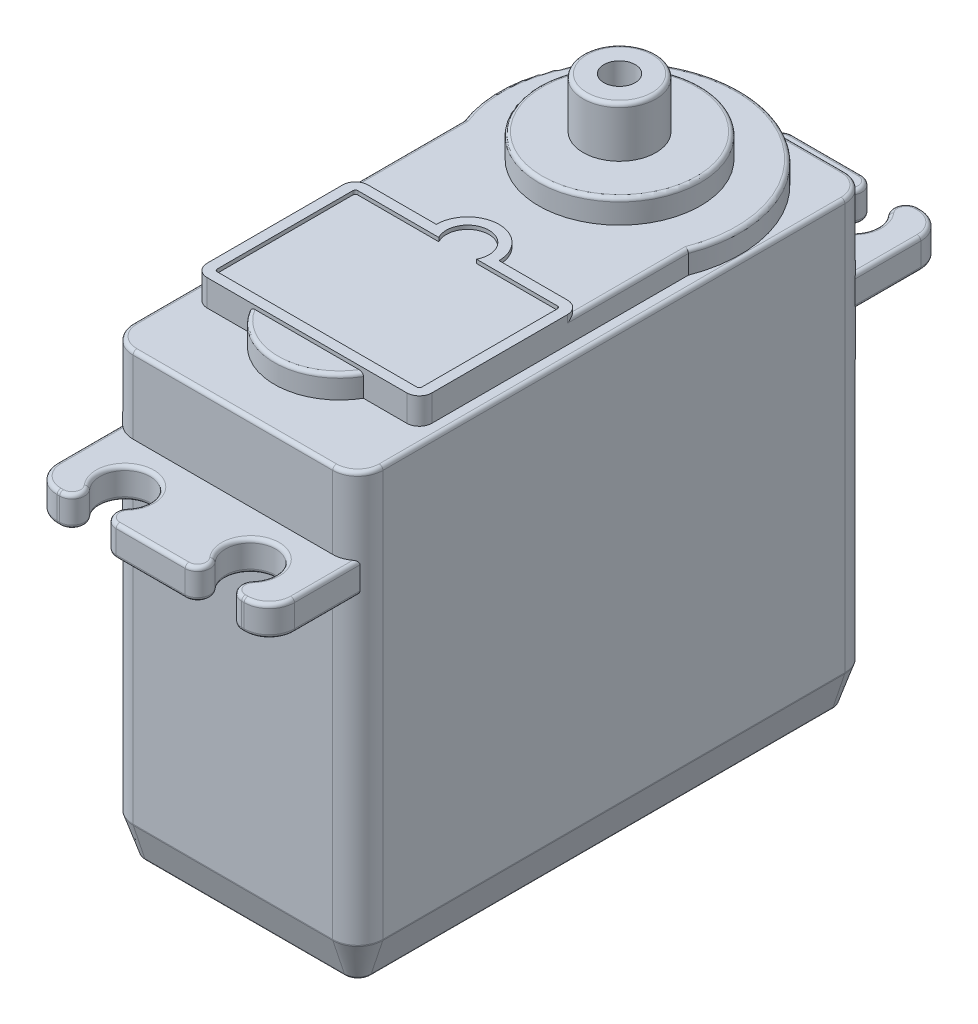
SolidWorks part; units mm, degrees
material "ABS"
ref_plane "Plan de face" through (0, 0, 0) normal (0, 0, 1) x (1, 0, 0)
ref_plane "Plan de dessus" through (0, 0, 0) normal (0, 1, 0) x (1, 0, 0)
ref_plane "Plan de droite" through (0, 0, 0) normal (1, 0, 0) x (0, 0, -1)
sketch "Esquisse1" plane through (0, 0, 0) normal (0, 1, 0) x (1, 0, 0)
  line L0 (0, 16.55) -> (0, -10.4) construction
  line L1 (0, -10.4) -> (9.95, -10.4) construction
  line L2 (-2.75, 16.55) -> (2.75, 16.55)
  line L3 (7.25, 16.55) -> (7.45, 16.55)
  line L4 (9.45, 14.55) -> (9.45, 9.3229)
  line L5 (-9.95, 8) -> (-9.95, -28.8)
  line L6 (9.95, 8) -> (9.95, -28.8)
  line L7 (-9.45, 14.55) -> (-9.45, 9.3229)
  line L8 (-7.25, 16.55) -> (-7.45, 16.55)
  line L9 (-7.25, -37.35) -> (-7.45, -37.35)
  line L10 (-9.45, -35.35) -> (-9.45, -30.1229)
  line L11 (9.45, -35.35) -> (9.45, -30.1229)
  line L12 (7.25, -37.35) -> (7.45, -37.35)
  line L13 (-2.75, -37.35) -> (2.75, -37.35)
  arc A0 (2.75, 16.55) -> (3.4932, 14.9151) centre (2.75, 15.5636) cw
  arc A1 (3.4932, 14.9151) -> (6.5068, 14.9151) centre (5, 13.6) ccw
  arc A2 (6.5068, 14.9151) -> (7.25, 16.55) centre (7.25, 15.5636) cw
  arc A3 (7.45, 16.55) -> (9.45, 14.55) centre (7.45, 14.55) cw
  arc A4 (9.95, 8) -> (9.45, 9.3229) centre (7.95, 8) ccw
  arc A5 (-9.95, 8) -> (-9.45, 9.3229) centre (-7.95, 8) cw
  arc A6 (-7.45, 16.55) -> (-9.45, 14.55) centre (-7.45, 14.55) ccw
  arc A7 (-6.5068, 14.9151) -> (-7.25, 16.55) centre (-7.25, 15.5636) ccw
  arc A8 (-3.4932, 14.9151) -> (-6.5068, 14.9151) centre (-5, 13.6) cw
  arc A9 (-2.75, 16.55) -> (-3.4932, 14.9151) centre (-2.75, 15.5636) ccw
  arc A10 (-2.75, -37.35) -> (-3.4932, -35.7151) centre (-2.75, -36.3636) cw
  arc A11 (-3.4932, -35.7151) -> (-6.5068, -35.7151) centre (-5, -34.4) ccw
  arc A12 (-6.5068, -35.7151) -> (-7.25, -37.35) centre (-7.25, -36.3636) cw
  arc A13 (-7.45, -37.35) -> (-9.45, -35.35) centre (-7.45, -35.35) cw
  arc A14 (-9.95, -28.8) -> (-9.45, -30.1229) centre (-7.95, -28.8) ccw
  arc A15 (9.95, -28.8) -> (9.45, -30.1229) centre (7.95, -28.8) cw
  arc A16 (7.45, -37.35) -> (9.45, -35.35) centre (7.45, -35.35) ccw
  arc A17 (6.5068, -35.7151) -> (7.25, -37.35) centre (7.25, -36.3636) ccw
  arc A18 (3.4932, -35.7151) -> (6.5068, -35.7151) centre (5, -34.4) cw
  arc A19 (2.75, -37.35) -> (3.4932, -35.7151) centre (2.75, -36.3636) ccw
  point P57 (-9.95, -10.4)
  dimension "D3" = 2
  dimension "D4" = 2
  dimension "D5" = 48
  dimension "D6" = 2
  dimension "D7" = 10
  dimension "D8" = 4.5
  dimension "D1" = 18.9
  dimension "D2" = 53.9
  dimension "D9" = 19.9
  dimension "D10" = 36.8
  dimension "D11" = 8
extrude "Extrusion1" add sketch "Esquisse1" along normal blind 2.4
sketch "Esquisse2" plane through (0, 0, 0) normal (0, 1, 0) x (1, 0, 0)
  line L0 (9.95, -28.8) -> (9.95, 8) construction
  line L1 (-9.95, 8) -> (-9.95, -28.8) construction
  line L2 (9.95, -28.8) -> (9.95, 8)
  line L3 (-9.95, 8) -> (-9.95, -28.8)
  line L4 (-7.95, 10) -> (7.95, 10)
  line L5 (-7.95, -30.8) -> (7.95, -30.8)
  arc A0 (-9.95, 8) -> (-7.95, 10) centre (-7.95, 8) cw
  arc A1 (9.95, 8) -> (7.95, 10) centre (7.95, 8) ccw
  arc A2 (9.95, 8) -> (9.45, 9.3229) centre (7.95, 8) ccw construction
  arc A3 (-9.45, 9.3229) -> (-9.95, 8) centre (-7.95, 8) ccw construction
  arc A4 (-9.95, -28.8) -> (-7.95, -30.8) centre (-7.95, -28.8) ccw
  arc A5 (9.95, -28.8) -> (7.95, -30.8) centre (7.95, -28.8) cw
  arc A6 (9.45, -30.1229) -> (9.95, -28.8) centre (7.95, -28.8) ccw construction
  arc A7 (-9.95, -28.8) -> (-9.45, -30.1229) centre (-7.95, -28.8) ccw construction
extrude "Extrusion2" add sketch "Esquisse2" along normal blind 8.5 and the other way blind 27.2
sketch "Esquisse3" plane through (0, 8.5, 0) normal (0, 1, 0) x (1, 0, 0)
  line L0 (7.95, 10) -> (-7.95, 10) construction
  line L1 (8.95, -3.4724) -> (8.95, -23.9)
  line L2 (7.95, -24.9) -> (4.5, -24.9)
  line L3 (0, 10) -> (0, -30.8) construction
  line L4 (-7.95, -30.8) -> (7.95, -30.8) construction
  line L5 (-7.95, -24.9) -> (-4.5, -24.9)
  line L6 (-8.95, -3.4724) -> (-8.95, -23.9)
  arc A0 (-8.95, -3.4724) -> (8.95, -3.4724) centre (0, 0) cw
  arc A1 (8.95, -23.9) -> (7.95, -24.9) centre (7.95, -23.9) cw
  arc A2 (4.5, -24.9) -> (-4.5, -24.9) centre (0, -22.2942) cw
  arc A3 (-8.95, -23.9) -> (-7.95, -24.9) centre (-7.95, -23.9) ccw
  dimension "D3" = 1
  dimension "D4" = 5.2
  dimension "D6" = 9.6
  dimension "D1" = 17.9
  dimension "D2" = 34.9
  dimension "D5" = 9
extrude "Extrusion3" add sketch "Esquisse3" along normal blind 1.8
sketch "Esquisse4" plane through (0, 10.3, 0) normal (0, 1, 0) x (1, 0, 0)
  line L0 (7.95, -24.9) -> (-7.95, -24.9)
  line L1 (-8.95, -23.9) -> (-8.95, -13.1)
  line L2 (-8.95, -3.4724) -> (-8.95, -23.9) construction
  line L3 (-7.95, -12.1) -> (-2.5, -12.1)
  line L4 (8.95, -23.9) -> (8.95, -3.4724) construction
  line L5 (8.95, -13.1) -> (8.95, -23.9)
  line L6 (7.95, -24.1) -> (-7.95, -24.1)
  line L7 (2.5, -12.1) -> (7.95, -12.1)
  line L8 (-8.15, -23.9) -> (-8.15, -13.1)
  line L9 (-7.95, -12.9) -> (-1.5, -12.9)
  line L10 (1.5, -12.9) -> (7.95, -12.9)
  line L11 (8.15, -13.1) -> (8.15, -23.9)
  arc A0 (-8.95, -23.9) -> (-7.95, -24.9) centre (-7.95, -23.9) ccw construction
  arc A1 (7.95, -24.9) -> (8.95, -23.9) centre (7.95, -23.9) ccw construction
  arc A2 (-8.95, -23.9) -> (-7.95, -24.9) centre (-7.95, -23.9) ccw
  arc A3 (7.95, -24.9) -> (8.95, -23.9) centre (7.95, -23.9) ccw
  arc A4 (-8.95, -13.1) -> (-7.95, -12.1) centre (-7.95, -13.1) cw
  arc A5 (7.95, -12.1) -> (8.95, -13.1) centre (7.95, -13.1) cw
  arc A6 (-2.5, -12.1) -> (2.5, -12.1) centre (0, -12.1) cw
  arc A7 (-8.15, -23.9) -> (-7.95, -24.1) centre (-7.95, -23.9) ccw
  arc A8 (-8.15, -13.1) -> (-7.95, -12.9) centre (-7.95, -13.1) cw
  arc A9 (-1.5, -12.9) -> (1.5, -12.9) centre (0, -12.1) cw
  arc A10 (7.95, -12.9) -> (8.15, -13.1) centre (7.95, -13.1) cw
  arc A11 (7.95, -24.1) -> (8.15, -23.9) centre (7.95, -23.9) ccw
  dimension "D2" = 2.5
  dimension "D1" = 12.8
  dimension "D3" = 0.8
extrude "Extrusion4" add sketch "Esquisse4" along normal blind 0.3
sketch "Esquisse5" plane through (0, 10.3, 0) normal (0, 1, 0) x (1, 0, 0)
  circle A0 centre (0, 0) radius 6.45
  dimension "D1" = 12.9
extrude "Extrusion5" add sketch "Esquisse5" along normal blind 1.9
sketch "Esquisse7" plane through (0, 12.2, 0) normal (0, 1, 0) x (-1, 0, 0)
  circle A0 centre (0, 0) radius 2.9
  dimension "D1" = 5.8
extrude "Extrusion6" add sketch "Esquisse7" along normal blind 4
hole_wizard "Trou taraudé M3x0.51" positions "Esquisse9" profile "Esquisse8" tap size "M3x0.5" standard "Ansi Métrique"
sketch "Esquisse9" plane through (0, 16.2, 0) normal (0, 1, 0) x (-1, 0, 0)
  point P0 (0, 0)
sketch "Esquisse8" plane through (0, 16.2, 0) normal (1, 0, 0) x (0, 0, 1)
  line L0 (0, 0) -> (0, 8.7511)
  line L1 (0, 8.7511) -> (1.25, 8)
  line L2 (1.25, 8) -> (1.25, 0)
  line L5 (1.25, 0) -> (0, 0)
  line L10 (0, 8.7511) -> (-1.25, 8) construction
  line L11 (0, -6.35) -> (0, 107.95) construction
  dimension "Diamètre du trou pour taraudage" = 2.5
  dimension "Profondeur du trou pour taraudage" = 8
  dimension "Angle de pointe" = 118
cosmetic thread "Filetage de perçage1" parameters "D1"=6, "D2"=3
chamfer "Chanfrein1" distance 1 distance2 3 8 edges at (0, -27.2, -10) (-9.3642, -27.2, -9.4142) (9.3642, -27.2, -9.4142) (-9.95, -27.2, 10.4) (9.95, -27.2, 10.4) (-9.3642, -27.2, 30.2142) (9.3642, -27.2, 30.2142) (0, -27.2, 30.8)
fillet "Congé5" radius 0.3 82 edges at (-9.45, 0, 32.7364) (-8.8642, 0, 36.7642) (-7.35, 0, 37.35) (-6.352, 0, 36.7718) (-5, 0, 32.4) (-3.648, 0, 36.7718) (0, 0, 37.35) (3.648, 0, 36.7718) (5, 0, 32.4) (6.352, 0, 36.7718) (7.35, 0, 37.35) (8.8642, 0, 36.7642) (-9.45, 2.4, 32.7364) (-8.8642, 2.4, 36.7642) (-7.35, 2.4, 37.35) (-6.352, 2.4, 36.7718) (-5, 2.4, 32.4) (-3.648, 2.4, 36.7718) (0, 2.4, 37.35) (3.648, 2.4, 36.7718) (5, 2.4, 32.4) (6.352, 2.4, 36.7718) (7.35, 2.4, 37.35) (8.8642, 2.4, 36.7642) (9.95, 8.5, 10.4) (9.3642, 8.5, 30.2142) (0, 8.5, 30.8) (-9.3642, 8.5, 30.2142) (9.3642, 8.5, -9.4142) (0, 8.5, -10) (-9.3642, 8.5, -9.4142) (9.45, 0, -11.9364) (8.8642, 0, -15.9642) (7.35, 0, -16.55) (6.352, 0, -15.9718) (5, 0, -11.6) (3.648, 0, -15.9718) (0, 0, -16.55) (-3.648, 0, -15.9718) (-5, 0, -11.6) (-6.352, 0, -15.9718) (-7.35, 0, -16.55) (-8.8642, 0, -15.9642) (9.45, 2.4, -11.9364) (8.8642, 2.4, -15.9642) (7.35, 2.4, -16.55) (6.352, 2.4, -15.9718) (5, 2.4, -11.6) (3.648, 2.4, -15.9718) (0, 2.4, -16.55) (-3.648, 2.4, -15.9718) (-5, 2.4, -11.6) (-6.352, 2.4, -15.9718) (-7.35, 2.4, -16.55) (-8.8642, 2.4, -15.9642) (9.45, 0, 32.7364) (9.45, 2.4, 32.7364) (0, 16.2, 2.9) (0, 12.2, 6.45) (0, 10.3, -9.6) (-9.95, 8.5, 10.4) (-9.45, 0, -11.9364) (-9.45, 2.4, -11.9364) (8.6571, -27.2, 29.5071) (8.95, -27.2, 10.4) (8.6571, -27.2, -8.7071) (0, -27.2, -9) (-8.6571, -27.2, -8.7071) (-8.95, -27.2, 10.4) (-8.6571, -27.2, 29.5071) (-9.3642, -24.2, 30.2142) (-9.95, -24.2, 10.4) (-9.3642, -24.2, -9.4142) (0, -24.2, -10) (9.3642, -24.2, -9.4142) (9.95, -24.2, 10.4) (9.3642, -24.2, 30.2142) (0, -27.2, 29.8) (0, -24.2, 30.8)
